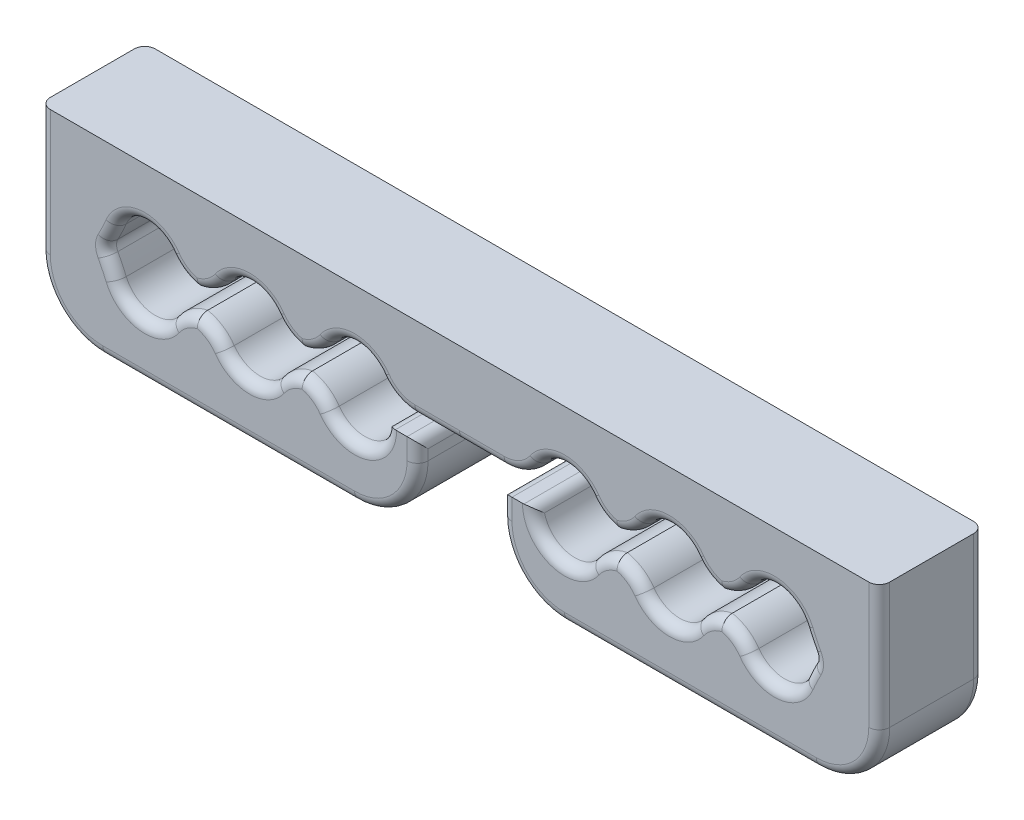
SolidWorks part; units mm, degrees
ref_plane "Front Plane" through (0, 0, 0) normal (0, 0, 1) x (1, 0, 0)
ref_plane "Top Plane" through (0, 0, 0) normal (0, 1, 0) x (1, 0, 0)
ref_plane "Right Plane" through (0, 0, 0) normal (1, 0, 0) x (0, 0, -1)
ref_axis "Axis1" through (0, 0, -88.99) along (0, 0, 1)
ref_axis "Axis2" through (-88.99, 0, 0) along (1, 0, 0)
ref_axis "Axis3" through (0, -55, 0) along (0, 1, 0)
sketch "Sketch3" plane through (0, 0, 0) normal (0, 0, 1) x (1, 0, 0)
  line L0 (-88.99, 0) -> (88.99, 0) construction
  line L4 (-20, 0) -> (-20, -4)
  line L5 (-20, -4) -> (-2, -4)
  line L7 (-13.5, 0) -> (-11.5, 0)
  line L8 (-8.5, 0) -> (-6.5, 0)
  line L9 (0, -55) -> (0, 55) construction
  line L10 (-2, -4) -> (-2, 0)
  line L11 (-3.5, 0) -> (-2, 0)
  line L12 (-20, 0.5) -> (0, 0.5) construction
  line L13 (-3.5, 1) -> (-2, 1)
  line L15 (-8.5, 1) -> (-6.5, 1)
  line L16 (-13.5, 1) -> (-11.5, 1)
  line L17 (-20, 5) -> (-2, 5)
  line L18 (-20, 1) -> (-20, 5)
  line L20 (-20, 1) -> (-20, 0)
  line L23 (-2, 5) -> (0, 5)
  line L24 (0, 5) -> (0, 1)
  line L25 (0, 1) -> (-2, 1)
  arc A0 (-6.5, 0) -> (-3.5, 0) centre (-5, 0) ccw
  arc A1 (-11.5, 0) -> (-8.5, 0) centre (-10, 0) ccw
  arc A2 (-16.5, 0) -> (-13.5, 0) centre (-15, 0) ccw
  arc A3 (-16.5, 1) -> (-13.5, 1) centre (-15, 1) cw
  arc A4 (-11.5, 1) -> (-8.5, 1) centre (-10, 1) cw
  arc A5 (-6.5, 1) -> (-3.5, 1) centre (-5, 1) cw
  arc A6 (-16.5, 1) -> (-16.5, 0) centre (-16.3087, 0.5) ccw
  point P0 (0, 0)
  dimension "D2" = 5
  dimension "D1" = 4
  dimension "D3" = 2
  dimension "D5" = 0.5
  dimension "D4" = 3
extrude "Boss-Extrude1" add sketch "Sketch3" along normal mid plane 5
fillet "Fillet1" radius 10 2 edges at (-16.5, 1, 0) (-16.5, 0, 0)
fillet "Fillet2" radius 2 9 edges at (-13.5, 1, 0) (-11.5, 1, 0) (-8.5, 1, 0) (-6.5, 1, 0) (-3.5, 1, 0) (-6.5, 0, 0) (-8.5, 0, 0) (-11.5, 0, 0) (-13.5, 0, 0)
fillet "Fillet3" radius 3 2 edges at (-20, -4, 0) (-2, -4, 0)
fillet "Fillet4" radius 0.5 50 edges at (-13.2152, -0.3215, -2.5) (-13.2152, 1.3215, -2.5) (-15.155, 2.492, -2.5) (-16.5709, 1.1651, -2.5) (-16.8441, 0.5, -2.5) (-16.5709, -0.1651, -2.5) (-13.2152, -0.3215, 2.5) (-13.2152, 1.3215, 2.5) (-15.155, 2.492, 2.5) (-16.5709, 1.1651, 2.5) (-16.8441, 0.5, 2.5) (-16.5709, -0.1651, 2.5) (-11.7848, 1.3215, -2.5) (-8.2152, 1.3215, -2.5) (-1.0639, 1, -2.5) (-6.7848, 1.3215, -2.5) (-5, 2.5, -2.5) (-8.2152, -0.3215, -2.5) (-11.7848, -0.3215, -2.5) (-6.7848, -0.3215, -2.5) (-6.7848, 1.3215, 2.5) (-1.0639, 1, 2.5) (-3.0535, 1.2272, 2.5) (-11.7848, 1.3215, 2.5) (-8.2152, 1.3215, 2.5) (-6.7848, -0.3215, 2.5) (-8.2152, -0.3215, 2.5) (-11.7848, -0.3215, 2.5) (-2, -0.5, -2.5) (-2.8787, -3.1213, -2.5) (-11, -4, -2.5) (-19.1213, -3.1213, -2.5) (-2, -0.5, 2.5) (-2.8787, -3.1213, 2.5) (-11, -4, 2.5) (-19.1213, -3.1213, 2.5) (-15.155, -1.492, -2.5) (-15.155, -1.492, 2.5) (-10, 2.5, -2.5) (-3.0535, 1.2272, -2.5) (-10, -1.5, -2.5) (-4.5508, -1.4312, -2.5) (-5, 2.5, 2.5) (-10, 2.5, 2.5) (-4.5508, -1.4312, 2.5) (-10, -1.5, 2.5) (-3.5, 0, 0) (-2, 0, 0) (-20, 2, -2.5) (-20, 2, 2.5)
mirror "Mirror1" about plane through (0, 0, 0) normal (1, 0, 0) of "Fillet3", "Fillet1", "Fillet2", "Fillet4", "Boss-Extrude1"
